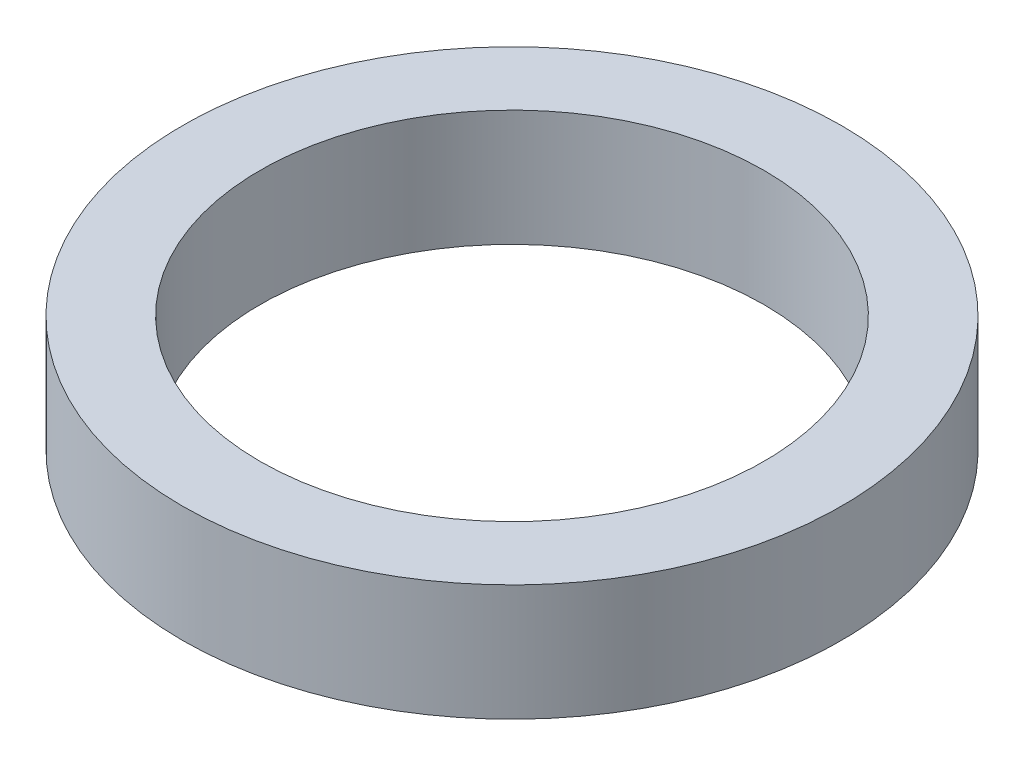
SolidWorks part; units mm, degrees
ref_plane "Front Plane" through (0, 0, 0) normal (0, 0, 1) x (1, 0, 0)
ref_plane "Top Plane" through (0, 0, 0) normal (0, 1, 0) x (1, 0, 0)
ref_plane "Right Plane" through (0, 0, 0) normal (1, 0, 0) x (0, 0, -1)
sketch "Sketch1" plane through (0, 0, 0) normal (0, 1, 0) x (1, 0, 0)
  circle A0 centre (0, 0) radius 42.5
  dimension "FLANGE_OD" = 85
extrude "Boss-Extrude1" add sketch "Sketch1" along normal blind 15
sketch "Sketch2" plane through (0, 0, 0) normal (0, 1, 0) x (1, 0, 0)
  circle A0 centre (0, 0) radius 32.5
  dimension "BORE_D" = 65
extrude "Cut-Extrude1" cut sketch "Sketch2" along normal through all
sketch "Sketch3" plane through (0, 15, 0) normal (0, 1, 0) x (1, 0, 0)
  circle A0 centre (0, 0) radius 17.7282 construction
  circle A1 centre (-17.7282, 0) radius 1.5362
  dimension "BOLT_D" = 3.0725
  dimension "BOLT_PCD" = 35.4564
extrude "Cut-Extrude2" cut sketch "Sketch3" against normal blind 13.8779 rebuild error yes
pattern_circular "CirPattern1" count 5 over 360 rebuild error yes
